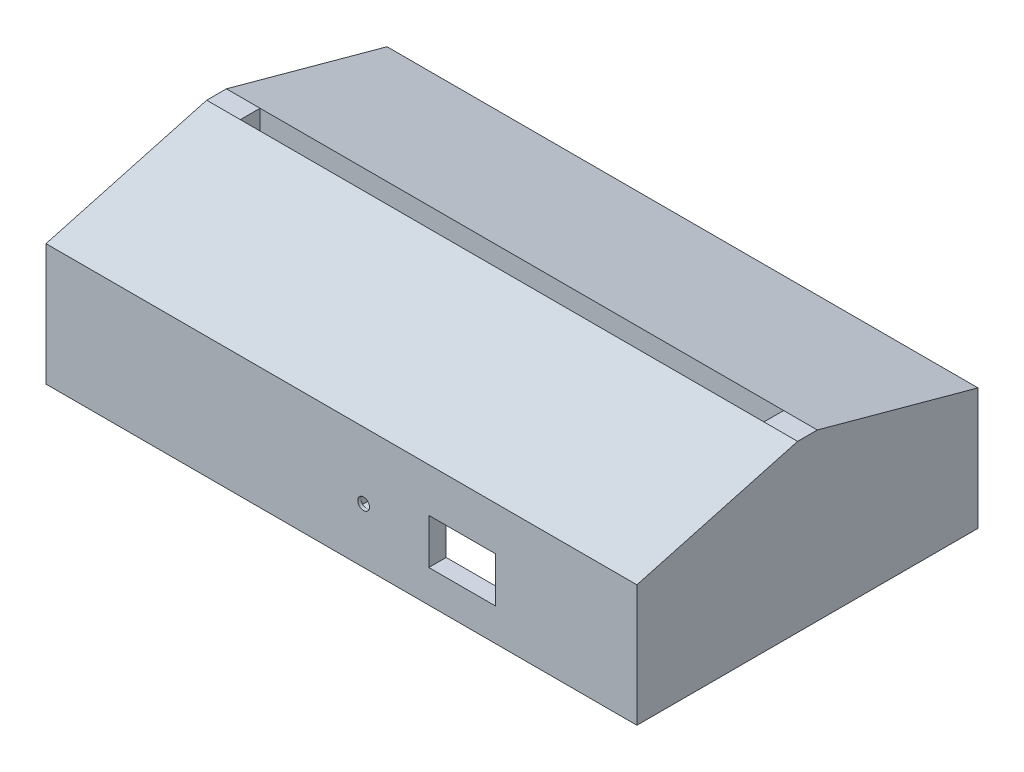
SolidWorks part; units mm, degrees
ref_plane "Front Plane" through (0, 0, 0) normal (0, 0, 1) x (1, 0, 0)
ref_plane "Top Plane" through (0, 0, 0) normal (0, 1, 0) x (1, 0, 0)
ref_plane "Right Plane" through (0, 0, 0) normal (1, 0, 0) x (0, 0, -1)
sketch "Sketch1" plane through (0, 0, 0) normal (0, 1, 0) x (1, 0, 0)
  line L1 (-86.36, 49.8475) -> (86.36, 49.8475)
  line L2 (-86.36, 49.8475) -> (-86.36, -49.8475)
  line L3 (-86.36, -49.8475) -> (86.36, -49.8475)
  line L4 (86.36, 49.8475) -> (86.36, -49.8475)
  line L5 (-86.36, 49.8475) -> (86.36, -49.8475) construction
  line L6 (-86.36, -49.8475) -> (86.36, 49.8475) construction
  point P0 (0, 0)
  dimension "D1" = 172.72
  dimension "D2" = 99.695
extrude "Boss-Extrude1" add sketch "Sketch1" along normal blind 38.1
sketch "Sketch2" plane through (0, 0, 0) normal (0, -1, 0) x (1, 0, 0)
  line L1 (-81.28, 44.7675) -> (81.28, 44.7675)
  line L2 (-81.28, 44.7675) -> (-81.28, -44.7675)
  line L3 (-81.28, -44.7675) -> (81.28, -44.7675)
  line L4 (81.28, 44.7675) -> (81.28, -44.7675)
  line L5 (-81.28, 44.7675) -> (81.28, -44.7675) construction
  line L6 (-81.28, -44.7675) -> (81.28, 44.7675) construction
  point P0 (0, 0)
  dimension "D1" = 162.56
  dimension "D2" = 89.535
extrude "Cut-Extrude1" cut sketch "Sketch2" against normal blind 31.75
sketch "Sketch3" plane through (0, 31.75, 0) normal (0, -1, 0) x (1, 0, 0)
  line L1 (-81.28, 44.7675) -> (-74.93, 44.7675)
  line L2 (-81.28, 44.7675) -> (-81.28, 38.4175)
  line L3 (-81.28, 38.4175) -> (-74.93, 38.4175)
  line L4 (-74.93, 44.7675) -> (-74.93, 38.4175)
  line L5 (81.28, -44.7675) -> (74.93, -44.7675)
  line L6 (81.28, -44.7675) -> (81.28, -38.4175)
  line L7 (81.28, -38.4175) -> (74.93, -38.4175)
  line L8 (74.93, -44.7675) -> (74.93, -38.4175)
  dimension "D1" = 6.35
  dimension "D2" = 6.35
  dimension "D3" = 6.35
  dimension "D4" = 6.35
extrude "Boss-Extrude2" add sketch "Sketch3" along normal blind 26.67
sketch "Sketch7" plane through (0, 5.08, 0) normal (0, -1, 0) x (1, 0, 0)
  line L0 (-74.93, 44.7675) -> (-81.28, 38.4175) construction
  line L1 (81.28, -38.4175) -> (74.93, -44.7675) construction
  circle A0 centre (-78.105, 41.5925) radius 1.5875
  circle A1 centre (78.105, -41.5925) radius 1.5875
extrude "Cut-Extrude3" cut sketch "Sketch7" against normal blind 26.67
sketch "Sketch8" plane through (0, 0, 49.8475) normal (0, 0, 1) x (1, 0, 0)
  line L0 (86.36, 0) -> (45.085, 0) construction
  line L1 (-86.36, 0) -> (86.36, 0) construction
  line L2 (45.085, 0) -> (45.085, 9.525) construction
  line L4 (45.085, 9.525) -> (25.527, 9.525)
  line L5 (45.085, 9.525) -> (45.085, 22.733)
  line L6 (45.085, 22.733) -> (25.527, 22.733)
  line L7 (25.527, 9.525) -> (25.527, 22.733)
  dimension "D1" = 41.275
  dimension "D2" = 9.525
  dimension "D3" = 13.208
  dimension "D4" = 19.558
extrude "Cut-Extrude4" cut sketch "Sketch8" against normal blind 5.08
sketch "Sketch9" plane through (0, 0, 49.8475) normal (0, 0, 1) x (1, 0, 0)
  line L0 (25.527, 16.129) -> (6.477, 16.129) construction
  line L1 (25.527, 22.733) -> (25.527, 9.525) construction
  line L3 (9.6266, 19.177) -> (3.3274, 19.177)
  line L4 (9.6266, 19.177) -> (9.6266, 13.081)
  line L5 (9.6266, 13.081) -> (3.3274, 13.081)
  line L6 (3.3274, 19.177) -> (3.3274, 13.081)
  line L7 (9.6266, 19.177) -> (3.3274, 13.081) construction
  line L8 (9.6266, 13.081) -> (3.3274, 19.177) construction
  circle A0 centre (6.477, 16.129) radius 1.7145
  dimension "D2" = 6.096
  dimension "D1" = 19.05
  dimension "D3" = 6.2992
extrude "Cut-Extrude6" cut sketch "Sketch9" against normal blind 3.4544 contours A0 region at (6.477, 16.129, 49.8475)
sketch "Sketch11" plane through (0, 0, 44.7675) normal (0, 0, -1) x (-1, 0, 0)
  line L0 (-9.6266, 25.273) -> (-3.3274, 25.273)
  line L1 (-9.6266, 13.081) -> (-3.3274, 13.081)
  line L2 (-9.6266, 13.081) -> (-9.6266, 25.273)
  line L5 (-3.3274, 25.273) -> (-3.3274, 13.081)
  dimension "D1" = 12.192
extrude "Cut-Extrude7" cut sketch "Sketch11" against normal blind 1.6256
sketch "Sketch14" plane through (0, 0, 44.7675) normal (0, 0, -1) x (-1, 0, 0)
  line L0 (-9.6266, 13.081) -> (-9.6266, 9.525)
  line L1 (-3.3274, 13.081) -> (-3.3274, 9.525)
  line L2 (-3.3274, 9.525) -> (-9.6266, 9.525)
  line L3 (-9.6266, 9.525) -> (-13.1826, 9.525)
  line L4 (-13.1826, 9.525) -> (-13.1826, 19.177)
  line L5 (-13.1826, 19.177) -> (-9.6266, 19.177)
  line L6 (-9.6266, 19.177) -> (-9.6266, 13.081)
  line L7 (-3.3274, 9.525) -> (0.2286, 9.525)
  line L8 (0.2286, 9.525) -> (0.2286, 19.177)
  line L9 (0.2286, 19.177) -> (-3.3274, 19.177)
  line L10 (-3.3274, 19.177) -> (-3.3274, 13.081)
  line M5 (-3.3274, 13.081) -> (-9.6266, 13.081)
  line M6 (-9.6266, 13.081) -> (-9.6266, 25.273)
  line M8 (-3.3274, 25.273) -> (-3.3274, 13.081)
  dimension "D1" = 3.556
  dimension "D2" = 3.556
  dimension "D3" = 9.652
  dimension "D4" = 3.556
extrude "Boss-Extrude3" add sketch "Sketch14" along normal blind 2.4384 contours L5 L4 L3 L0 M6 | L2 L1 L0 M5 | L8 L9 L1 L7 M8 region at (6.477, 11.303, 44.7675) region at (11.4046, 14.351, 44.7675) region at (1.5494, 14.351, 44.7675)
sketch "Sketch22" plane through (0, 0, 46.3931) normal (0, 0, -1) x (-1, 0, 0)
  line L0 (-4.7625, 16.129) -> (-4.7625, 14.4145) construction
  line L1 (-4.7625, 14.4145) -> (-6.477, 14.4145) construction
  line L2 (-6.477, 14.4145) -> (-6.477, 25.273) construction
  line L3 (-4.7625, 14.4145) -> (-8.1915, 14.4145)
  line L4 (-4.7625, 14.4145) -> (-4.7625, 25.273)
  line L5 (-4.7625, 25.273) -> (-8.1915, 25.273)
  line L6 (-8.1915, 14.4145) -> (-8.1915, 25.273)
  line L7 (-3.3274, 25.273) -> (-9.6266, 25.273) construction
  circle A0 centre (-6.477, 16.129) radius 1.7145 construction
  dimension "D1" = 3.429
  dimension "D2" = 10.8585
extrude "Cut-Extrude8" cut sketch "Sketch22" against normal blind 2.54
sketch "Sketch25" plane through (0, 0, 42.3291) normal (0, 0, -1) x (-1, 0, 0)
  line L0 (-9.6266, 13.081) -> (-8.4201, 13.081) construction
  line L1 (-9.6266, 13.081) -> (-3.3274, 13.081) construction
  line L2 (-3.3274, 13.081) -> (-4.5339, 13.081) construction
  line L3 (-3.3274, 13.081) -> (-9.6266, 13.081) construction
  line L4 (-13.1826, 19.177) -> (-9.6266, 19.177) construction
  line L5 (-8.4201, 13.081) -> (-9.6266, 13.081)
  line L9 (-4.5339, 13.081) -> (-3.3274, 13.081)
  line L13 (-11.4046, 19.177) -> (-9.6266, 19.177)
  line L14 (-11.4046, 19.177) -> (-11.4046, 13.081)
  line L15 (-11.4046, 13.081) -> (-9.6266, 13.081)
  line L16 (-9.6266, 19.177) -> (-9.6266, 13.081)
  line L17 (0.2286, 19.177) -> (-3.3274, 19.177) construction
  line L18 (-1.5494, 19.177) -> (-3.3274, 19.177)
  line L19 (-1.5494, 19.177) -> (-1.5494, 13.081)
  line L20 (-1.5494, 13.081) -> (-3.3274, 13.081)
  line L21 (-3.3274, 19.177) -> (-3.3274, 13.081)
  line L23 (-9.6266, 13.081) -> (-9.9441, 13.081)
  line L27 (-3.3274, 13.081) -> (-3.0734, 13.081)
  line L31 (-8.4201, 13.081) -> (-9.9441, 13.081)
  line L32 (-8.4201, 13.081) -> (-8.4201, 11.811)
  line L33 (-8.4201, 11.811) -> (-9.9441, 11.811)
  line L34 (-9.9441, 13.081) -> (-9.9441, 11.811)
  line L35 (-4.5339, 13.081) -> (-3.0099, 13.081)
  line L36 (-4.5339, 13.081) -> (-4.5339, 11.811)
  line L37 (-4.5339, 11.811) -> (-3.0099, 11.811)
  line L38 (-3.0099, 13.081) -> (-3.0099, 11.811)
  line M4 (-9.6266, 19.177) -> (-13.1826, 19.177)
  line M8 (0.2286, 19.177) -> (-3.3274, 19.177)
  line M9 (-3.3274, 19.177) -> (-3.3274, 13.081)
  line M10 (-3.3274, 13.081) -> (-9.6266, 13.081)
  line M11 (-9.6266, 13.081) -> (-9.6266, 19.177)
  dimension "D1" = 1.2065
  dimension "D2" = 1.2065
  dimension "D3" = 1.524
  dimension "D4" = 1.524
extrude "Boss-Extrude16" add sketch "Sketch25" along normal blind 2.54 contours L14 L15 M11 M4 | L20 L19 M8 M9 region at (10.5156, 16.129, 42.3291) region at (2.4384, 16.129, 42.3291)
extrude "Boss-Extrude18" add sketch "Sketch25<7>" along normal blind 2.54 contours L15 L34 L33 L32 M10 | L38 L20 L36 L37 M10 region at (9.1821, 12.446, 42.3291) region at (3.7719, 12.446, 42.3291)
sketch "Sketch25<7>" plane through (0, 0, 42.3291) normal (0, 0, -1) x (-1, 0, 0) same geometry as "Sketch25"
sketch "Sketch28" plane through (3.3274, 0, 0) normal (1, 0, 0) x (0, 0, -1)
  line L0 (-39.7891, 19.177) -> (-42.3291, 19.177) construction
  line L2 (-39.7891, 19.177) -> (-44.7675, 19.177) construction
  line L4 (-42.3291, 19.177) -> (-42.3291, 13.081) construction
  line L5 (-46.3931, 13.081) -> (-39.7891, 13.081) construction
  line L7 (-39.7891, 19.177) -> (-42.3291, 19.177)
  line L8 (-39.7891, 19.177) -> (-39.7891, 13.081)
  line L9 (-39.7891, 13.081) -> (-42.3291, 13.081)
  line L10 (-42.3291, 19.177) -> (-42.3291, 13.081)
  dimension "D1" = 2.54
sketch "Sketch29" plane through (9.6266, 0, 0) normal (-1, 0, 0) x (0, 0, 1)
  line L0 (39.7891, 19.177) -> (42.3291, 19.177) construction
  line L1 (39.7891, 19.177) -> (44.7675, 19.177) construction
  line L2 (42.3291, 19.177) -> (42.3291, 13.081) construction
  line L3 (46.3931, 13.081) -> (39.7891, 13.081) construction
  line L5 (39.7891, 19.177) -> (42.3291, 19.177)
  line L6 (39.7891, 19.177) -> (39.7891, 13.081)
  line L7 (39.7891, 13.081) -> (42.3291, 13.081)
  line L8 (42.3291, 19.177) -> (42.3291, 13.081)
  dimension "D1" = 2.54
extrude "Boss-Extrude19" add sketch "Sketch28" along normal blind 1.2065
extrude "Boss-Extrude20" add sketch "Sketch29" along normal blind 1.2065
sketch "Sketch30" plane through (9.9441, 0, 0) normal (1, 0, 0) x (0, 0, -1)
  line L0 (-39.7891, 13.081) -> (-42.3291, 11.811)
  line L1 (-42.3291, 11.811) -> (-39.7891, 11.811)
  line L2 (-39.7891, 11.811) -> (-39.7891, 13.081)
extrude "Cut-Extrude12" cut sketch "Sketch30" against normal blind 7.0485
sketch "Sketch33" plane through (0, 0, 49.8475) normal (0, 0, 1) x (1, 0, 0)
  line L0 (86.36, 38.1) -> (86.36, 35.56) construction
  line L1 (86.36, 38.1) -> (86.36, 0) construction
  line L3 (-86.36, 38.1) -> (86.36, 38.1)
  line L4 (-86.36, 38.1) -> (-86.36, 35.56)
  line L5 (-86.36, 35.56) -> (86.36, 35.56)
  line L6 (86.36, 38.1) -> (86.36, 35.56)
  dimension "D1" = 2.54
extrude "Cut-Extrude13" cut sketch "Sketch33" against normal through all
sketch "Sketch36" plane through (0, 35.56, 0) normal (0, 1, 0) x (1, 0, 0)
  line L0 (-86.36, 49.8475) -> (-86.36, -49.8475) construction
  line L1 (86.36, 49.8475) -> (-86.36, 49.8475)
  line L2 (86.36, 49.8475) -> (86.36, 2.8829)
  line L3 (86.36, 2.8829) -> (-86.36, 2.8829)
  line L4 (-86.36, 49.8475) -> (-86.36, 2.8829)
  line L6 (86.36, -49.8475) -> (-86.36, -49.8475)
  line L7 (86.36, -49.8475) -> (86.36, -2.8829)
  line L8 (86.36, -2.8829) -> (-86.36, -2.8829)
  line L9 (-86.36, -49.8475) -> (-86.36, -2.8829)
  dimension "D1" = 46.9646
  dimension "D2" = 46.9646
extrude "Boss-Extrude21" add sketch "Sketch36" along normal blind 12.827
sketch "Sketch37" plane through (-86.36, 0, 0) normal (-1, 0, 0) x (0, 0, 1)
  line L0 (-49.8475, 48.387) -> (-49.8475, 35.56) construction
  line L1 (-49.8475, 48.387) -> (-49.8475, 0) construction
  line L2 (-49.8475, 35.56) -> (-49.8475, 48.387)
  line L3 (-49.8475, 48.387) -> (-2.8829, 48.387)
  line L4 (-2.8829, 48.387) -> (-49.8475, 35.56)
  line L7 (0, 35.56) -> (0, 48.387) construction
  line L8 (-2.8829, 35.56) -> (2.8829, 35.56) construction
  line L9 (2.8829, 48.387) -> (49.8475, 35.56)
  line L10 (49.8475, 35.56) -> (49.8475, 48.387)
  line L11 (49.8475, 48.387) -> (2.8829, 48.387)
  dimension "D1" = 12.827
extrude "Cut-Extrude14" cut sketch "Sketch37" against normal through all
sketch "Sketch41" plane through (0, 35.56, 0) normal (0, 1, 0) x (1, 0, 0)
  line L0 (86.36, -2.8829) -> (-86.36, -2.8829) construction
  line L1 (-86.36, 2.8829) -> (-76.5175, 2.8829)
  line L2 (-86.36, 2.8829) -> (-86.36, -2.8829)
  line L3 (-86.36, -2.8829) -> (-76.5175, -2.8829)
  line L4 (-76.5175, 2.8829) -> (-76.5175, -2.8829)
  line L5 (-86.36, 2.8829) -> (86.36, 2.8829) construction
  line L6 (86.36, -2.8829) -> (76.5175, -2.8829)
  line L7 (86.36, -2.8829) -> (86.36, 2.8829)
  line L8 (86.36, 2.8829) -> (76.5175, 2.8829)
  line L9 (76.5175, -2.8829) -> (76.5175, 2.8829)
  dimension "D1" = 9.8425
  dimension "D2" = 9.8425
extrude "Boss-Extrude22" add sketch "Sketch41" along normal through all
sketch "Sketch42" plane through (0, 35.56, 0) normal (0, 1, 0) x (1, 0, 0)
  line L0 (-76.5175, 0) -> (-63.8175, 0) construction
  line L1 (-76.5175, -2.8829) -> (-76.5175, 2.8829) construction
  line L2 (76.5175, 0) -> (63.8175, 0) construction
  line L3 (76.5175, 2.8829) -> (76.5175, -2.8829) construction
  line L4 (-63.8175, 0) -> (63.8175, 0) construction
  circle A0 centre (-63.8175, 0) radius 2.2225
  circle A1 centre (63.8175, 0) radius 2.2225
  circle A2 centre (-38.4175, 0) radius 2.2225
  circle A3 centre (-13.0175, 0) radius 2.2225
  circle A4 centre (12.3825, 0) radius 2.2225
  circle A5 centre (37.7825, 0) radius 2.2225
  dimension "D2" = 12.7
  dimension "D3" = 5
  dimension "D1" = 12.7
extrude "Cut-Extrude15" cut sketch "Sketch42" against normal through all
sketch "Sketch44" plane through (0, 31.75, 0) normal (0, -1, 0) x (-1, 0, 0)
  line L0 (63.8175, -2.2225) -> (63.8175, -4.7625) construction
  line L1 (42.7482, -7.3025) -> (34.0868, -7.3025)
  line L2 (68.1482, -7.3025) -> (59.4868, -7.3025)
  line L3 (68.1482, -7.3025) -> (68.1482, -2.2225)
  line L4 (68.1482, -2.2225) -> (59.4868, -2.2225)
  line L5 (59.4868, -7.3025) -> (59.4868, -2.2225)
  line L6 (68.1482, -7.3025) -> (59.4868, -2.2225) construction
  line L7 (68.1482, -2.2225) -> (59.4868, -7.3025) construction
  line L8 (34.0868, -7.3025) -> (34.0868, -2.2225)
  line L9 (42.7482, -2.2225) -> (34.0868, -2.2225)
  line L10 (42.7482, -7.3025) -> (42.7482, -2.2225)
  line L11 (17.3482, -7.3025) -> (8.6868, -7.3025)
  line L12 (8.6868, -7.3025) -> (8.6868, -2.2225)
  line L13 (17.3482, -2.2225) -> (8.6868, -2.2225)
  line L14 (17.3482, -7.3025) -> (17.3482, -2.2225)
  line L15 (-8.0518, -7.3025) -> (-16.7132, -7.3025)
  line L16 (-16.7132, -7.3025) -> (-16.7132, -2.2225)
  line L17 (-8.0518, -2.2225) -> (-16.7132, -2.2225)
  line L18 (-8.0518, -7.3025) -> (-8.0518, -2.2225)
  line L19 (-33.4518, -7.3025) -> (-42.1132, -7.3025)
  line L20 (-42.1132, -7.3025) -> (-42.1132, -2.2225)
  line L21 (-33.4518, -2.2225) -> (-42.1132, -2.2225)
  line L22 (-33.4518, -7.3025) -> (-33.4518, -2.2225)
  line L23 (-59.6138, -7.3025) -> (-68.2752, -7.3025)
  line L24 (-59.6138, -7.3025) -> (-59.6138, -2.2225)
  line L25 (-59.6138, -2.2225) -> (-68.2752, -2.2225)
  line L26 (-68.2752, -7.3025) -> (-68.2752, -2.2225)
  circle A0 centre (63.8175, 0) radius 2.2225 construction
  dimension "D1" = 2.54
  dimension "D2" = 8.6614
  dimension "D3" = 5
  dimension "D4" = 2
extrude "Boss-Extrude24" add sketch "Sketch44" along normal blind 10.541
sketch "Sketch46" plane through (0, 0, 2.2225) normal (0, 0, -1) x (-1, 0, 0)
  line L0 (68.1482, 21.209) -> (59.4868, 21.209) construction
  line L1 (68.1482, 31.75) -> (66.6242, 31.75)
  line L2 (68.1482, 31.75) -> (68.1482, 21.209)
  line L3 (68.1482, 21.209) -> (66.6242, 21.209)
  line L4 (66.6242, 31.75) -> (66.6242, 21.209)
  line L5 (42.7482, 31.75) -> (42.7482, 21.209)
  line L6 (59.4868, 31.75) -> (61.0108, 31.75)
  line L7 (59.4868, 31.75) -> (59.4868, 21.209)
  line L8 (59.4868, 21.209) -> (61.0108, 21.209)
  line L9 (61.0108, 31.75) -> (61.0108, 21.209)
  line L10 (42.7482, 21.209) -> (41.2242, 21.209)
  line L11 (42.7482, 31.75) -> (41.2242, 31.75)
  line L12 (41.2242, 31.75) -> (41.2242, 21.209)
  line L13 (35.6108, 31.75) -> (35.6108, 21.209)
  line L14 (34.0868, 21.209) -> (35.6108, 21.209)
  line L15 (34.0868, 31.75) -> (34.0868, 21.209)
  line L16 (34.0868, 31.75) -> (35.6108, 31.75)
  line L17 (17.3482, 31.75) -> (17.3482, 21.209)
  line L18 (17.3482, 21.209) -> (15.8242, 21.209)
  line L19 (17.3482, 31.75) -> (15.8242, 31.75)
  line L20 (15.8242, 31.75) -> (15.8242, 21.209)
  line L21 (10.2108, 31.75) -> (10.2108, 21.209)
  line L22 (8.6868, 21.209) -> (10.2108, 21.209)
  line L23 (8.6868, 31.75) -> (8.6868, 21.209)
  line L24 (8.6868, 31.75) -> (10.2108, 31.75)
  line L25 (-8.0518, 31.75) -> (-8.0518, 21.209)
  line L26 (-8.0518, 21.209) -> (-9.5758, 21.209)
  line L27 (-8.0518, 31.75) -> (-9.5758, 31.75)
  line L28 (-9.5758, 31.75) -> (-9.5758, 21.209)
  line L29 (-15.1892, 31.75) -> (-15.1892, 21.209)
  line L30 (-16.7132, 21.209) -> (-15.1892, 21.209)
  line L31 (-16.7132, 31.75) -> (-16.7132, 21.209)
  line L32 (-16.7132, 31.75) -> (-15.1892, 31.75)
  line L33 (-33.4518, 31.75) -> (-33.4518, 21.209)
  line L34 (-33.4518, 21.209) -> (-34.9758, 21.209)
  line L35 (-33.4518, 31.75) -> (-34.9758, 31.75)
  line L36 (-34.9758, 31.75) -> (-34.9758, 21.209)
  line L37 (-40.5892, 31.75) -> (-40.5892, 21.209)
  line L38 (-42.1132, 21.209) -> (-40.5892, 21.209)
  line L39 (-42.1132, 31.75) -> (-42.1132, 21.209)
  line L40 (-42.1132, 31.75) -> (-40.5892, 31.75)
  line L41 (-59.6138, 31.75) -> (-59.6138, 21.209)
  line L42 (-61.1378, 31.75) -> (-61.1378, 21.209)
  line L43 (-59.6138, 21.209) -> (-61.1378, 21.209)
  line L44 (-59.6138, 31.75) -> (-61.1378, 31.75)
  line L45 (-68.2752, 31.75) -> (-66.7512, 31.75)
  line L46 (-66.7512, 31.75) -> (-66.7512, 21.209)
  line L47 (-68.2752, 31.75) -> (-68.2752, 21.209)
  line L48 (-68.2752, 21.209) -> (-66.7512, 21.209)
  dimension "D1" = 1.524
  dimension "D2" = 1.524
  dimension "D3" = 5
  dimension "D4" = 2
extrude "Boss-Extrude25" add sketch "Sketch46" along normal blind 5.6134
sketch "Sketch48" plane through (66.7512, 0, 0) normal (-1, 0, 0) x (0, 0, 1)
  line L0 (2.2225, 21.209) -> (2.2225, 31.75) construction
  line L1 (-3.3909, 21.209) -> (2.2225, 21.209)
  line L2 (-3.3909, 21.209) -> (-3.3909, 23.114)
  line L3 (-3.3909, 23.114) -> (2.2225, 23.114)
  line L4 (2.2225, 21.209) -> (2.2225, 23.114)
  dimension "D1" = 1.905
sketch "Sketch49" plane through (61.1378, 0, 0) normal (1, 0, 0) x (0, 0, -1)
  line L0 (-2.2225, 31.75) -> (-2.2225, 21.209) construction
  line L1 (3.3909, 21.209) -> (-2.2225, 21.209)
  line L2 (3.3909, 21.209) -> (3.3909, 23.114)
  line L3 (3.3909, 23.114) -> (-2.2225, 23.114)
  line L4 (-2.2225, 21.209) -> (-2.2225, 23.114)
  dimension "D1" = 1.905
sketch "Sketch50" plane through (40.5892, 0, 0) normal (-1, 0, 0) x (0, 0, 1)
  line L0 (2.2225, 21.209) -> (2.2225, 31.75) construction
  line L1 (-3.3909, 21.209) -> (2.2225, 21.209)
  line L2 (-3.3909, 21.209) -> (-3.3909, 23.114)
  line L3 (-3.3909, 23.114) -> (2.2225, 23.114)
  line L4 (2.2225, 21.209) -> (2.2225, 23.114)
  dimension "D1" = 1.905
sketch "Sketch51" plane through (34.9758, 0, 0) normal (1, 0, 0) x (0, 0, -1)
  line L0 (-2.2225, 31.75) -> (-2.2225, 21.209) construction
  line L1 (3.3909, 21.209) -> (-2.2225, 21.209)
  line L2 (3.3909, 21.209) -> (3.3909, 23.114)
  line L3 (3.3909, 23.114) -> (-2.2225, 23.114)
  line L4 (-2.2225, 21.209) -> (-2.2225, 23.114)
  dimension "D1" = 1.905
sketch "Sketch52" plane through (15.1892, 0, 0) normal (-1, 0, 0) x (0, 0, 1)
  line L0 (2.2225, 21.209) -> (2.2225, 31.75) construction
  line L1 (-3.3909, 21.209) -> (2.2225, 21.209)
  line L2 (-3.3909, 21.209) -> (-3.3909, 23.114)
  line L3 (-3.3909, 23.114) -> (2.2225, 23.114)
  line L4 (2.2225, 21.209) -> (2.2225, 23.114)
  dimension "D1" = 1.905
sketch "Sketch53" plane through (9.5758, 0, 0) normal (1, 0, 0) x (0, 0, -1)
  line L0 (-2.2225, 31.75) -> (-2.2225, 21.209) construction
  line L1 (3.3909, 21.209) -> (-2.2225, 21.209)
  line L2 (3.3909, 21.209) -> (3.3909, 23.114)
  line L3 (3.3909, 23.114) -> (-2.2225, 23.114)
  line L4 (-2.2225, 21.209) -> (-2.2225, 23.114)
  dimension "D1" = 1.905
sketch "Sketch54" plane through (-10.2108, 0, 0) normal (-1, 0, 0) x (0, 0, 1)
  line L0 (2.2225, 21.209) -> (2.2225, 31.75) construction
  line L1 (-3.3909, 21.209) -> (2.2225, 21.209)
  line L2 (-3.3909, 21.209) -> (-3.3909, 23.114)
  line L3 (-3.3909, 23.114) -> (2.2225, 23.114)
  line L4 (2.2225, 21.209) -> (2.2225, 23.114)
  dimension "D1" = 1.905
sketch "Sketch55" plane through (-15.8242, 0, 0) normal (1, 0, 0) x (0, 0, -1)
  line L0 (-2.2225, 31.75) -> (-2.2225, 21.209) construction
  line L1 (3.3909, 21.209) -> (-2.2225, 21.209)
  line L2 (3.3909, 21.209) -> (3.3909, 23.114)
  line L3 (3.3909, 23.114) -> (-2.2225, 23.114)
  line L4 (-2.2225, 21.209) -> (-2.2225, 23.114)
  dimension "D1" = 1.905
sketch "Sketch56" plane through (-35.6108, 0, 0) normal (-1, 0, 0) x (0, 0, 1)
  line L0 (2.2225, 21.209) -> (2.2225, 31.75) construction
  line L1 (-3.3909, 21.209) -> (2.2225, 21.209)
  line L2 (-3.3909, 21.209) -> (-3.3909, 23.114)
  line L3 (-3.3909, 23.114) -> (2.2225, 23.114)
  line L4 (2.2225, 21.209) -> (2.2225, 23.114)
  dimension "D1" = 1.905
sketch "Sketch57" plane through (-41.2242, 0, 0) normal (1, 0, 0) x (0, 0, -1)
  line L0 (-2.2225, 31.75) -> (-2.2225, 21.209) construction
  line L1 (3.3909, 21.209) -> (-2.2225, 21.209)
  line L2 (3.3909, 21.209) -> (3.3909, 23.114)
  line L3 (3.3909, 23.114) -> (-2.2225, 23.114)
  line L4 (-2.2225, 21.209) -> (-2.2225, 23.114)
  dimension "D1" = 1.905
sketch "Sketch58" plane through (-61.0108, 0, 0) normal (-1, 0, 0) x (0, 0, 1)
  line L0 (2.2225, 21.209) -> (2.2225, 31.75) construction
  line L1 (-3.3909, 21.209) -> (2.2225, 21.209)
  line L2 (-3.3909, 21.209) -> (-3.3909, 23.114)
  line L3 (-3.3909, 23.114) -> (2.2225, 23.114)
  line L4 (2.2225, 21.209) -> (2.2225, 23.114)
  dimension "D1" = 1.905
sketch "Sketch59" plane through (-66.6242, 0, 0) normal (1, 0, 0) x (0, 0, -1)
  line L0 (-2.2225, 31.75) -> (-2.2225, 21.209) construction
  line L1 (3.3909, 21.209) -> (-2.2225, 21.209)
  line L2 (3.3909, 21.209) -> (3.3909, 23.114)
  line L3 (3.3909, 23.114) -> (-2.2225, 23.114)
  line L4 (-2.2225, 21.209) -> (-2.2225, 23.114)
  dimension "D1" = 1.905
extrude "Boss-Extrude26" add sketch "Sketch48" along normal blind 1.27
extrude "Boss-Extrude27" add sketch "Sketch49" along normal blind 1.27
extrude "Boss-Extrude28" add sketch "Sketch50" along normal blind 1.27
extrude "Boss-Extrude29" add sketch "Sketch51" along normal blind 1.27
extrude "Boss-Extrude30" add sketch "Sketch52" along normal blind 1.27
extrude "Boss-Extrude31" add sketch "Sketch53" along normal blind 1.27
extrude "Boss-Extrude32" add sketch "Sketch54" along normal blind 1.27
extrude "Boss-Extrude33" add sketch "Sketch55" along normal blind 1.27
extrude "Boss-Extrude34" add sketch "Sketch56" along normal blind 1.27
extrude "Boss-Extrude35" add sketch "Sketch57" along normal blind 1.27
extrude "Boss-Extrude36" add sketch "Sketch58" along normal blind 1.27
extrude "Boss-Extrude37" add sketch "Sketch59" along normal blind 1.27
